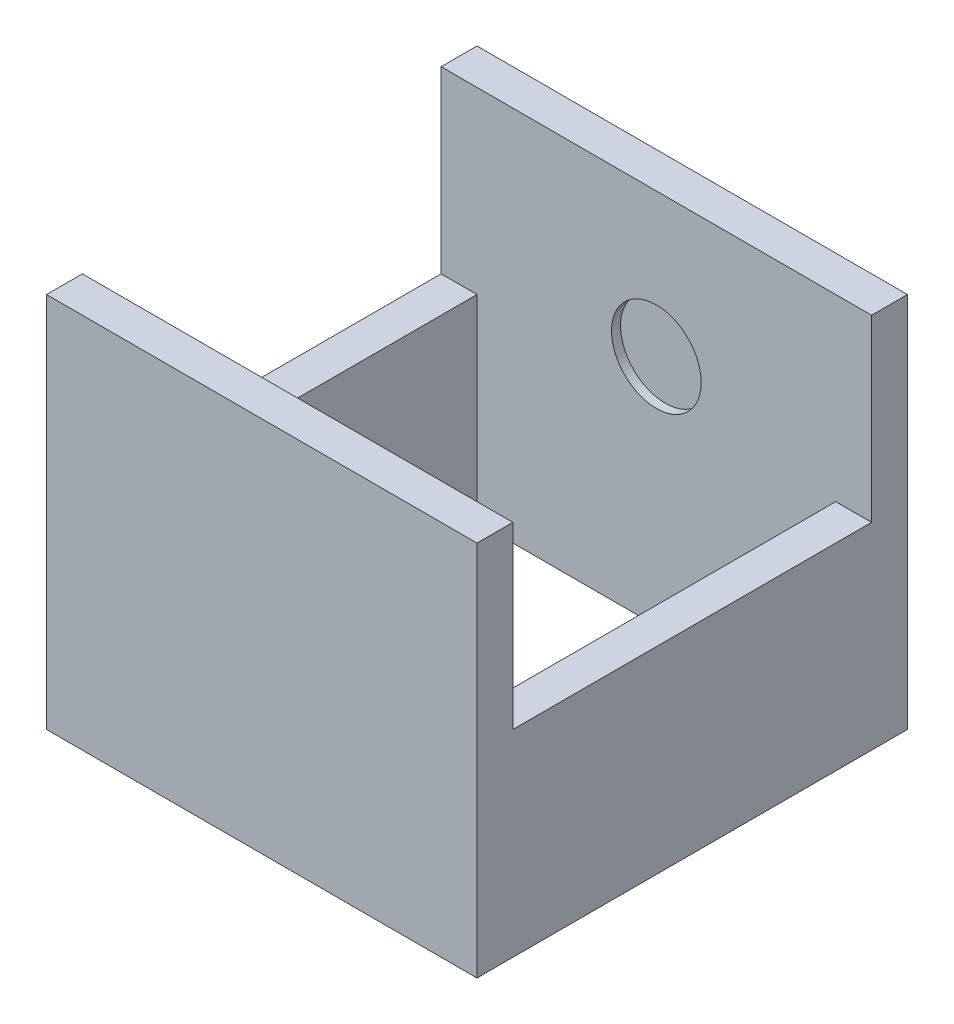
SolidWorks part; units mm, degrees
material "ABS"
ref_plane "Front Plane" through (0, 0, 0) normal (0, 0, 1) x (1, 0, 0)
ref_plane "Top Plane" through (0, 0, 0) normal (0, 1, 0) x (1, 0, 0)
ref_plane "Right Plane" through (0, 0, 0) normal (1, 0, 0) x (0, 0, -1)
sketch "Sketch7" plane through (0, 0, 0) normal (0, 1, 0) x (1, 0, 0)
  line L1 (-120, -120) -> (120, -120)
  line L2 (-120, -120) -> (-120, 120)
  line L3 (-120, 120) -> (120, 120)
  line L4 (120, -120) -> (120, 120)
  line L5 (-120, -120) -> (120, 120) construction
  line L6 (-120, 120) -> (120, -120) construction
  point P0 (0, 0)
  point P6 (0, 0)
  dimension "D1" = 240
  dimension "D2" = 240
extrude "Boss-Extrude3" add sketch "Sketch7" along normal blind 210
sketch "Sketch9" plane through (0, 0, 0) normal (0, 0, 1) x (1, 0, 0)
  line L1 (0, 210) -> (0, 130) construction
  line L2 (-120, 210) -> (120, 210) construction
  circle A0 centre (0, 130) radius 25
  point P2 (0, 210)
  dimension "D2" = 50
  dimension "D1" = 80
extrude "Cut-Extrude3" cut sketch "Sketch9" against normal mid plane 210
sketch "Sketch10" plane through (0, 0, 0) normal (0, -1, 0) x (1, 0, 0)
  line L0 (-120, 120) -> (120, 120) construction
  line L1 (-100, -100) -> (100, -100)
  line L2 (-100, -100) -> (-100, 100)
  line L3 (-100, 100) -> (100, 100)
  line L4 (100, -100) -> (100, 100)
  line L5 (-100, -100) -> (100, 100) construction
  line L6 (-100, 100) -> (100, -100) construction
  line L7 (120, 120) -> (120, -120) construction
  point P0 (0, 0)
  dimension "D1" = 20
  dimension "D2" = 20
extrude "Cut-Extrude4" cut sketch "Sketch10" against normal blind 210
sketch "Sketch12" plane through (-100, 0, 0) normal (1, 0, 0) x (0, 0, -1)
  line L0 (-100, 210) -> (-100, 0) construction
  line L1 (100, 210) -> (-100, 210)
  line L2 (100, 210) -> (100, 110)
  line L3 (100, 110) -> (-100, 110)
  line L4 (-100, 210) -> (-100, 110)
  dimension "D1" = 100
extrude "Cut-Extrude6" cut sketch "Sketch12" against normal through all both and the other way through all
